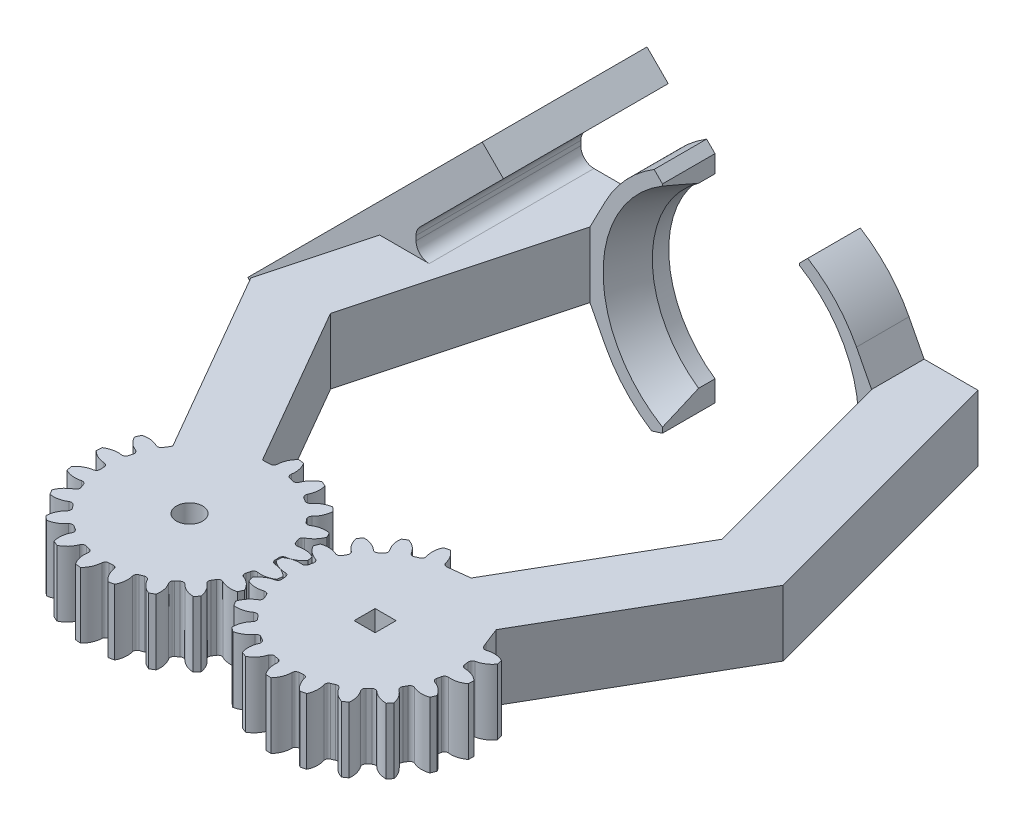
SolidWorks part; units mm, degrees
ref_plane "Front Plane" through (0, 0, 0) normal (0, 0, 1) x (1, 0, 0)
ref_plane "Top Plane" through (0, 0, 0) normal (0, 1, 0) x (1, 0, 0)
ref_plane "Right Plane" through (0, 0, 0) normal (1, 0, 0) x (0, 0, -1)
sketch "Sketch1" plane through (0, 0, 0) normal (0, 1, 0) x (1, 0, 0)
  line L0 (-1.5124, 12.6196) -> (-15.6699, 37.141)
  line L1 (-10.1727, 7.6196) -> (-25.6699, 34.4615)
  line L2 (29.9646, 12.9427) -> (43.9355, 37.141)
  line L3 (38.6794, 8.0371) -> (53.9355, 34.4615)
  line L4 (-13.3963, -7.7344) -> (-13.3913, -7.7315)
  line L5 (-13.1804, -8.0969) -> (-13.6023, -7.3661)
  line L6 (-10.3506, -11.4955) -> (-10.3468, -11.4912)
  line L7 (-10.0332, -11.7735) -> (-10.6603, -11.209)
  line L8 (-6.2917, -14.1314) -> (-6.2894, -14.1261)
  line L9 (-5.904, -14.2977) -> (-6.6748, -13.9546)
  line L10 (-1.6169, -15.384) -> (-1.6163, -15.3783)
  line L11 (-1.1968, -15.4224) -> (-2.0359, -15.3342)
  line L12 (3.2161, -15.1307) -> (3.2149, -15.1251)
  line L13 (3.6276, -15.0374) -> (2.8023, -15.2128)
  line L14 (7.7344, -13.3963) -> (7.7315, -13.3913)
  line L15 (8.0969, -13.1804) -> (7.3661, -13.6023)
  line L16 (11.4955, -10.3506) -> (11.4912, -10.3468)
  line L17 (11.7735, -10.0332) -> (11.209, -10.6603)
  line L18 (14.1314, -6.2917) -> (14.1261, -6.2894)
  line L19 (14.2977, -5.904) -> (13.9546, -6.6748)
  line L20 (15.384, -1.6169) -> (15.3783, -1.6163)
  line L21 (15.4224, -1.1968) -> (15.3342, -2.0359)
  line L22 (15.1307, 3.2161) -> (15.1251, 3.2149)
  line L23 (15.0374, 3.6276) -> (15.2128, 2.8023)
  line L24 (13.3963, 7.7344) -> (13.3913, 7.7315)
  line L25 (13.1804, 8.0969) -> (13.6023, 7.3661)
  line L26 (10.3506, 11.4955) -> (10.3468, 11.4912)
  line L27 (10.0332, 11.7735) -> (10.6603, 11.209)
  line L28 (6.2917, 14.1314) -> (6.2894, 14.1261)
  line L29 (5.904, 14.2977) -> (6.6748, 13.9546)
  line L30 (1.6169, 15.384) -> (1.6163, 15.3783)
  line L31 (1.1968, 15.4224) -> (2.0359, 15.3342)
  line L32 (-14.1314, 6.2917) -> (-14.1261, 6.2894)
  line L33 (-14.2977, 5.904) -> (-13.9546, 6.6748)
  line L34 (-15.384, 1.6169) -> (-15.3783, 1.6163)
  line L35 (-15.4224, 1.1968) -> (-15.3342, 2.0359)
  line L36 (-15.1307, -3.2161) -> (-15.1251, -3.2149)
  line L37 (-15.0374, -3.6276) -> (-15.2128, -2.8023)
  line L38 (-9.6435, -8.1965) -> (-10.0224, -7.7286)
  line L39 (-6.6387, -10.7754) -> (-7.1436, -10.4475)
  line L40 (-2.984, -12.2995) -> (-3.5655, -12.1436)
  line L41 (0.9628, -12.6196) -> (0.3616, -12.6511)
  line L42 (4.8154, -11.7044) -> (4.2533, -11.9202)
  line L43 (8.1965, -9.6435) -> (7.7286, -10.0224)
  line L44 (10.7754, -6.6387) -> (10.4475, -7.1436)
  line L45 (12.2995, -2.984) -> (12.1436, -3.5655)
  line L46 (12.6196, 0.9628) -> (12.6511, 0.3616)
  line L47 (11.7044, 4.8154) -> (11.9202, 4.2533)
  line L48 (9.6435, 8.1965) -> (10.0224, 7.7286)
  line L49 (6.6387, 10.7754) -> (7.1436, 10.4475)
  line L50 (2.984, 12.2995) -> (3.5655, 12.1436)
  line L51 (-0.9628, 12.6196) -> (-0.3616, 12.6511)
  line L52 (-10.7754, 6.6387) -> (-10.4475, 7.1436)
  line L53 (-12.2995, 2.984) -> (-12.1436, 3.5655)
  line L54 (-12.6196, -0.9628) -> (-12.6511, -0.3616)
  line L55 (-11.7044, -4.8154) -> (-11.9202, -4.2533)
  line L56 (43.7132, -0.8096) -> (43.7074, -0.8093)
  line L57 (43.6854, -1.2306) -> (43.7295, -0.388)
  line L58 (42.707, -5.5435) -> (42.7016, -5.5414)
  line L59 (42.5504, -5.9353) -> (42.8528, -5.1476)
  line L60 (40.2871, -9.7348) -> (40.2826, -9.7312)
  line L61 (40.0172, -10.059) -> (40.5481, -9.4033)
  line L62 (36.6905, -12.9732) -> (36.6874, -12.9684)
  line L63 (36.3336, -13.1981) -> (37.0412, -12.7386)
  line L64 (32.2693, -14.9417) -> (32.2678, -14.9361)
  line L65 (31.8603, -15.0453) -> (32.6753, -14.8269)
  line L66 (27.4561, -15.4476) -> (27.4564, -15.4418)
  line L67 (27.0351, -15.4197) -> (27.8777, -15.4639)
  line L68 (22.7221, -14.4413) -> (22.7242, -14.436)
  line L69 (22.3303, -14.2848) -> (23.1181, -14.5871)
  line L70 (18.5308, -12.0215) -> (18.5345, -12.017)
  line L71 (18.2066, -11.7515) -> (18.8623, -12.2825)
  line L72 (15.2925, -8.4249) -> (15.2973, -8.4218)
  line L73 (15.0675, -8.0679) -> (15.5271, -8.7756)
  line L74 (13.324, -4.0036) -> (13.3295, -4.0021)
  line L75 (13.2203, -3.5946) -> (13.4387, -4.4096)
  line L76 (12.8181, 0.8096) -> (12.8238, 0.8093)
  line L77 (12.8459, 1.2306) -> (12.8018, 0.388)
  line L78 (13.8243, 5.5435) -> (13.8297, 5.5414)
  line L79 (13.9809, 5.9353) -> (13.6785, 5.1476)
  line L80 (16.2442, 9.7348) -> (16.2486, 9.7312)
  line L81 (16.5141, 10.059) -> (15.9831, 9.4033)
  line L82 (19.8408, 12.9732) -> (19.8439, 12.9684)
  line L83 (20.1977, 13.1981) -> (19.4901, 12.7386)
  line L84 (24.262, 14.9417) -> (24.2635, 14.9361)
  line L85 (24.671, 15.0453) -> (23.856, 14.8269)
  line L86 (43.2073, 4.0036) -> (43.2018, 4.0021)
  line L87 (43.3109, 3.5946) -> (43.0926, 4.4096)
  line L88 (40.5792, -2.9251) -> (40.7044, -2.3362)
  line L89 (39.0727, -6.5871) -> (39.3737, -6.0656)
  line L90 (36.5082, -9.6042) -> (36.9557, -9.2013)
  line L91 (33.1369, -11.6812) -> (33.687, -11.4363)
  line L92 (29.2888, -12.6148) -> (29.8876, -12.5519)
  line L93 (25.3405, -12.3136) -> (25.9295, -12.4388)
  line L94 (21.6786, -10.807) -> (22.2, -11.1081)
  line L95 (18.6614, -8.2426) -> (19.0643, -8.69)
  line L96 (16.5844, -4.8713) -> (16.8293, -5.4213)
  line L97 (15.6508, -1.0232) -> (15.7138, -1.622)
  line L98 (15.9521, 2.9251) -> (15.8269, 2.3362)
  line L99 (17.4586, 6.5871) -> (17.1576, 6.0656)
  line L100 (20.0231, 9.6042) -> (19.5756, 9.2013)
  line L101 (23.3944, 11.6812) -> (22.8443, 11.4363)
  line L102 (27.2425, 12.6148) -> (26.6437, 12.5519)
  line L103 (39.9469, 4.8713) -> (39.702, 5.4213)
  line L104 (40.8805, 1.0232) -> (40.8175, 1.622)
  line L105 (27.2425, 12.6148) -> (29.9646, 12.9427)
  line L106 (39.702, 5.4213) -> (38.6794, 8.0371)
  line L107 (-10.4475, 7.1436) -> (-10.1727, 7.6196)
  line L108 (-0.9628, 12.6196) -> (-1.5124, 12.6196)
  line L109 (-15.6699, 37.141) -> (-5.3171, 75.778)
  line L110 (-5.3171, 75.778) -> (-14.9764, 78.3662)
  line L111 (-14.9764, 78.3662) -> (-26.4012, 35.7282)
  line L112 (-25.6699, 34.4615) -> (-26.4012, 35.7282)
  line L113 (43.9355, 37.141) -> (33.5828, 75.778)
  line L114 (33.5828, 75.778) -> (43.242, 78.3662)
  line L115 (43.242, 78.3662) -> (54.6668, 35.7282)
  line L116 (53.9355, 34.4615) -> (54.6668, 35.7282)
  circle A0 centre (0, 0) radius 2
  circle A1 centre (28.2656, 0) radius 2
  arc A2 (-13.1804, -8.0969) -> (-10.7748, -7.6007) centre (-12.61, -4.7824) ccw
  arc A3 (-10.0224, -7.7286) -> (-10.7748, -7.6007) centre (-10.4679, -8.0721) ccw
  arc A4 (-11.9698, -5.5309) -> (-13.6023, -7.3661) centre (-10.4467, -8.5294) ccw
  arc A5 (-11.9698, -5.5309) -> (-11.7044, -4.8154) centre (-12.2246, -5.0294) ccw
  arc A6 (-10.0332, -11.7735) -> (-7.8987, -10.5583) centre (-10.515, -8.4451) ccw
  arc A7 (-7.1436, -10.4475) -> (-7.8987, -10.5583) centre (-7.4611, -10.9118) ccw
  arc A8 (-9.6749, -8.9591) -> (-10.6603, -11.209) centre (-7.2997, -11.3401) ccw
  arc A9 (-9.6749, -8.9591) -> (-9.6435, -8.1965) centre (-10.0721, -8.5608) ccw
  arc A10 (-5.904, -14.2977) -> (-4.2494, -12.4824) centre (-7.3907, -11.281) ccw
  arc A11 (-3.5655, -12.1436) -> (-4.2494, -12.4824) centre (-3.724, -12.6833) ccw
  arc A12 (-6.4328, -11.5103) -> (-6.6748, -13.9546) centre (-3.4381, -13.0408) ccw
  arc A13 (-6.4328, -11.5103) -> (-6.6387, -10.7754) centre (-6.9337, -11.2543) ccw
  arc A14 (-1.1968, -15.4224) -> (-0.1841, -13.1846) centre (-3.5429, -13.0127) ccw
  arc A15 (0.3616, -12.6511) -> (-0.1841, -13.1846) centre (0.3776, -13.2134) ccw
  arc A16 (-2.5611, -12.9348) -> (-2.0359, -15.3342) centre (0.76, -13.465) ccw
  arc A17 (-2.5611, -12.9348) -> (-2.984, -12.2995) centre (-3.1166, -12.8461) ccw
  arc A18 (3.6276, -15.0374) -> (3.8991, -12.5962) centre (0.6517, -13.4707) ccw
  arc A19 (4.2533, -11.9202) -> (3.8991, -12.5962) centre (4.4423, -12.45) ccw
  arc A20 (1.5613, -13.0931) -> (2.8023, -15.2128) centre (4.8837, -12.5711) ccw
  arc A21 (1.5613, -13.0931) -> (0.9628, -12.6196) centre (1.0056, -13.1804) ccw
  arc A22 (8.0969, -13.1804) -> (7.6007, -10.7748) centre (4.7824, -12.61) ccw
  arc A23 (7.7286, -10.0224) -> (7.6007, -10.7748) centre (8.0721, -10.4679) ccw
  arc A24 (5.5309, -11.9698) -> (7.3661, -13.6023) centre (8.5294, -10.4467) ccw
  arc A25 (5.5309, -11.9698) -> (4.8154, -11.7044) centre (5.0294, -12.2246) ccw
  arc A26 (11.7735, -10.0332) -> (10.5583, -7.8987) centre (8.4451, -10.515) ccw
  arc A27 (10.4475, -7.1436) -> (10.5583, -7.8987) centre (10.9118, -7.4611) ccw
  arc A28 (8.9591, -9.6749) -> (11.209, -10.6603) centre (11.3401, -7.2997) ccw
  arc A29 (8.9591, -9.6749) -> (8.1965, -9.6435) centre (8.5608, -10.0721) ccw
  arc A30 (14.2977, -5.904) -> (12.4824, -4.2494) centre (11.281, -7.3907) ccw
  arc A31 (12.1436, -3.5655) -> (12.4824, -4.2494) centre (12.6833, -3.724) ccw
  arc A32 (11.5103, -6.4328) -> (13.9546, -6.6748) centre (13.0408, -3.4381) ccw
  arc A33 (11.5103, -6.4328) -> (10.7754, -6.6387) centre (11.2543, -6.9337) ccw
  arc A34 (15.4224, -1.1968) -> (13.1846, -0.1841) centre (13.0127, -3.5429) ccw
  arc A35 (12.6511, 0.3616) -> (13.1846, -0.1841) centre (13.2134, 0.3776) ccw
  arc A36 (12.9348, -2.5611) -> (15.3342, -2.0359) centre (13.465, 0.76) ccw
  arc A37 (12.9348, -2.5611) -> (12.2995, -2.984) centre (12.8461, -3.1166) ccw
  arc A38 (15.0374, 3.6276) -> (12.5962, 3.8991) centre (13.4707, 0.6517) ccw
  arc A39 (11.9202, 4.2533) -> (12.5962, 3.8991) centre (12.45, 4.4423) ccw
  arc A40 (13.0931, 1.5613) -> (15.2128, 2.8023) centre (12.5711, 4.8837) ccw
  arc A41 (13.0931, 1.5613) -> (12.6196, 0.9628) centre (13.1804, 1.0056) ccw
  arc A42 (13.1804, 8.0969) -> (10.7748, 7.6007) centre (12.61, 4.7824) ccw
  arc A43 (10.0224, 7.7286) -> (10.7748, 7.6007) centre (10.4679, 8.0721) ccw
  arc A44 (11.9698, 5.5309) -> (13.6023, 7.3661) centre (10.4467, 8.5294) ccw
  arc A45 (11.9698, 5.5309) -> (11.7044, 4.8154) centre (12.2246, 5.0294) ccw
  arc A46 (10.0332, 11.7735) -> (7.8987, 10.5583) centre (10.515, 8.4451) ccw
  arc A47 (7.1436, 10.4475) -> (7.8987, 10.5583) centre (7.4611, 10.9118) ccw
  arc A48 (9.6749, 8.9591) -> (10.6603, 11.209) centre (7.2997, 11.3401) ccw
  arc A49 (9.6749, 8.9591) -> (9.6435, 8.1965) centre (10.0721, 8.5608) ccw
  arc A50 (5.904, 14.2977) -> (4.2494, 12.4824) centre (7.3907, 11.281) ccw
  arc A51 (3.5655, 12.1436) -> (4.2494, 12.4824) centre (3.724, 12.6833) ccw
  arc A52 (6.4328, 11.5103) -> (6.6748, 13.9546) centre (3.4381, 13.0408) ccw
  arc A53 (6.4328, 11.5103) -> (6.6387, 10.7754) centre (6.9337, 11.2543) ccw
  arc A54 (1.1968, 15.4224) -> (0.1841, 13.1846) centre (3.5429, 13.0127) ccw
  arc A55 (-0.3616, 12.6511) -> (0.1841, 13.1846) centre (-0.3776, 13.2134) ccw
  arc A56 (2.5611, 12.9348) -> (2.0359, 15.3342) centre (-0.76, 13.465) ccw
  arc A57 (2.5611, 12.9348) -> (2.984, 12.2995) centre (3.1166, 12.8461) ccw
  arc A58 (-14.2977, 5.904) -> (-12.4824, 4.2494) centre (-11.281, 7.3907) ccw
  arc A59 (-12.1436, 3.5655) -> (-12.4824, 4.2494) centre (-12.6833, 3.724) ccw
  arc A60 (-11.5103, 6.4328) -> (-13.9546, 6.6748) centre (-13.0408, 3.4381) ccw
  arc A61 (-11.5103, 6.4328) -> (-10.7754, 6.6387) centre (-11.2543, 6.9337) ccw
  arc A62 (-15.4224, 1.1968) -> (-13.1846, 0.1841) centre (-13.0127, 3.5429) ccw
  arc A63 (-12.6511, -0.3616) -> (-13.1846, 0.1841) centre (-13.2134, -0.3776) ccw
  arc A64 (-12.9348, 2.5611) -> (-15.3342, 2.0359) centre (-13.465, -0.76) ccw
  arc A65 (-12.9348, 2.5611) -> (-12.2995, 2.984) centre (-12.8461, 3.1166) ccw
  arc A66 (-15.0374, -3.6276) -> (-12.5962, -3.8991) centre (-13.4707, -0.6517) ccw
  arc A67 (-11.9202, -4.2533) -> (-12.5962, -3.8991) centre (-12.45, -4.4423) ccw
  arc A68 (-13.0931, -1.5613) -> (-15.2128, -2.8023) centre (-12.5711, -4.8837) ccw
  arc A69 (-13.0931, -1.5613) -> (-12.6196, -0.9628) centre (-13.1804, -1.0056) ccw
  arc A70 (41.3167, -1.8806) -> (43.6854, -1.2306) centre (41.6724, 1.4636) ccw
  arc A71 (41.3167, -1.8806) -> (40.7044, -2.3362) centre (41.2572, -2.44) ccw
  arc A72 (43.7295, -0.388) -> (41.4418, 0.5061) centre (41.446, -2.857) ccw
  arc A73 (40.8805, 1.0232) -> (41.4418, 0.5061) centre (41.4411, 1.0686) ccw
  arc A74 (40.0968, -5.8216) -> (42.5504, -5.9353) centre (41.4685, -2.7509) ccw
  arc A75 (40.0968, -5.8216) -> (39.3737, -6.0656) centre (39.8674, -6.3352) ccw
  arc A76 (42.8528, -5.1476) -> (40.9533, -3.5903) centre (39.918, -6.7901) ccw
  arc A77 (40.5792, -2.9251) -> (40.9533, -3.5903) centre (41.1265, -3.0551) ccw
  arc A78 (37.7188, -9.1927) -> (40.0172, -10.059) centre (39.9722, -6.6962) ccw
  arc A79 (37.7188, -9.1927) -> (36.9557, -9.2013) centre (37.3419, -9.6103) ccw
  arc A80 (40.5481, -9.4033) -> (39.2229, -7.3353) centre (37.2494, -10.0586) ccw
  arc A81 (39.0727, -6.5871) -> (39.2229, -7.3353) centre (39.553, -6.8798) ccw
  arc A82 (34.4154, -11.664) -> (36.3336, -13.1981) centre (37.33, -9.986) ccw
  arc A83 (34.4154, -11.664) -> (33.687, -11.4363) centre (33.9279, -11.9446) ccw
  arc A84 (37.0412, -12.7386) -> (36.4199, -10.3623) centre (33.7015, -12.3424) ccw
  arc A85 (36.5082, -9.6042) -> (36.4199, -10.3623) centre (36.8745, -10.0311) ccw
  arc A86 (30.51, -12.9935) -> (31.8603, -15.0453) centre (33.8006, -12.2983) ccw
  arc A87 (30.51, -12.9935) -> (29.8876, -12.5519) centre (29.9597, -13.1097) ccw
  arc A88 (32.6753, -14.8269) -> (32.8187, -12.3749) centre (29.6214, -13.4181) ccw
  arc A89 (33.1369, -11.6812) -> (32.8187, -12.3749) centre (33.3534, -12.2004) ccw
  arc A90 (26.385, -13.0511) -> (27.0351, -15.4197) centre (29.7293, -13.4068) ccw
  arc A91 (26.385, -13.0511) -> (25.9295, -12.4388) centre (25.8256, -12.9916) ccw
  arc A92 (27.8777, -15.4639) -> (28.7718, -13.1762) centre (25.4086, -13.1803) ccw
  arc A93 (29.2888, -12.6148) -> (28.7718, -13.1762) centre (29.3343, -13.1755) ccw
  arc A94 (22.444, -11.8312) -> (22.3303, -14.2848) centre (25.5147, -13.2029) ccw
  arc A95 (22.444, -11.8312) -> (22.2, -11.1081) centre (21.9304, -11.6017) ccw
  arc A96 (23.1181, -14.5871) -> (24.6753, -12.6877) centre (21.4755, -11.6524) ccw
  arc A97 (25.3405, -12.3136) -> (24.6753, -12.6877) centre (25.2105, -12.8609) ccw
  arc A98 (19.0729, -9.4531) -> (18.2066, -11.7515) centre (21.5695, -11.7066) ccw
  arc A99 (19.0729, -9.4531) -> (19.0643, -8.69) centre (18.6554, -9.0762) ccw
  arc A100 (18.8623, -12.2825) -> (20.9304, -10.9573) centre (18.2071, -8.9838) ccw
  arc A101 (21.6786, -10.807) -> (20.9304, -10.9573) centre (21.3858, -11.2873) ccw
  arc A102 (16.6017, -6.1498) -> (15.0675, -8.0679) centre (18.2796, -9.0644) ccw
  arc A103 (16.6017, -6.1498) -> (16.8293, -5.4213) centre (16.321, -5.6623) ccw
  arc A104 (15.5271, -8.7756) -> (17.9034, -8.1542) centre (15.9232, -5.4358) ccw
  arc A105 (18.6614, -8.2426) -> (17.9034, -8.1542) centre (18.2346, -8.6089) ccw
  arc A106 (15.2722, -2.2444) -> (13.2203, -3.5946) centre (15.9673, -5.5349) ccw
  arc A107 (15.2722, -2.2444) -> (15.7138, -1.622) centre (15.1559, -1.6941) ccw
  arc A108 (13.4387, -4.4096) -> (15.8908, -4.553) centre (14.8475, -1.3558) ccw
  arc A109 (16.5844, -4.8713) -> (15.8908, -4.553) centre (16.0652, -5.0878) ccw
  arc A110 (15.2146, 1.8806) -> (12.8459, 1.2306) centre (14.8589, -1.4636) ccw
  arc A111 (15.2146, 1.8806) -> (15.8269, 2.3362) centre (15.274, 2.44) ccw
  arc A112 (12.8018, 0.388) -> (15.0895, -0.5061) centre (15.0853, 2.857) ccw
  arc A113 (15.6508, -1.0232) -> (15.0895, -0.5061) centre (15.0902, -1.0686) ccw
  arc A114 (16.4345, 5.8216) -> (13.9809, 5.9353) centre (15.0628, 2.7509) ccw
  arc A115 (16.4345, 5.8216) -> (17.1576, 6.0656) centre (16.6639, 6.3352) ccw
  arc A116 (13.6785, 5.1476) -> (15.578, 3.5903) centre (16.6133, 6.7901) ccw
  arc A117 (15.9521, 2.9251) -> (15.578, 3.5903) centre (15.4048, 3.0551) ccw
  arc A118 (18.8125, 9.1927) -> (16.5141, 10.059) centre (16.559, 6.6962) ccw
  arc A119 (18.8125, 9.1927) -> (19.5756, 9.2013) centre (19.1894, 9.6103) ccw
  arc A120 (15.9831, 9.4033) -> (17.3084, 7.3353) centre (19.2818, 10.0586) ccw
  arc A121 (17.4586, 6.5871) -> (17.3084, 7.3353) centre (16.9783, 6.8798) ccw
  arc A122 (22.1159, 11.664) -> (20.1977, 13.1981) centre (19.2012, 9.986) ccw
  arc A123 (22.1159, 11.664) -> (22.8443, 11.4363) centre (22.6034, 11.9446) ccw
  arc A124 (19.4901, 12.7386) -> (20.1114, 10.3623) centre (22.8298, 12.3424) ccw
  arc A125 (20.0231, 9.6042) -> (20.1114, 10.3623) centre (19.6567, 10.0311) ccw
  arc A126 (26.0212, 12.9935) -> (24.671, 15.0453) centre (22.7307, 12.2983) ccw
  arc A127 (26.0212, 12.9935) -> (26.6437, 12.5519) centre (26.5716, 13.1097) ccw
  arc A128 (23.856, 14.8269) -> (23.7126, 12.3749) centre (26.9099, 13.4181) ccw
  arc A129 (23.3944, 11.6812) -> (23.7126, 12.3749) centre (23.1779, 12.2004) ccw
  arc A130 (41.2591, 2.2444) -> (43.3109, 3.5946) centre (40.5639, 5.5349) ccw
  arc A131 (41.2591, 2.2444) -> (40.8175, 1.622) centre (41.3754, 1.6941) ccw
  arc A132 (43.0926, 4.4096) -> (40.6405, 4.553) centre (41.6837, 1.3558) ccw
  arc A133 (39.9469, 4.8713) -> (40.6405, 4.553) centre (40.466, 5.0878) ccw
extrude "Boss-Extrude1" add sketch "Sketch1" along normal blind 10 contours A133 L103 L106 L3 L116 L115 L114 L113 L2 L105 L102 A127 A126 L85 A128 A129 L101 A123 A122 L83 A124 A125 L100 A119 A118 L81 A120 A121 L99 A115 A114 L79 A116 A117 L98 A111 A110 L77 A112 A113 L97 A107 A106 L75 A108 | A69 A68 L37 A66 A67 L55 A5 A4 L5 A2 A3 L38 A9 A8 L7 A6 A7 L39 A13 A12 L9 A10 A11 L40 A17 A16 L11 A14 A15 L41 A21 A20 L13 A18 A19 L42 A25 A24 L15 A22 A23 L43 A29 A28 region at (-8.072, 0, -23.4532) region at (36.3461, 0, -23.5032)
sketch "Sketch2" plane through (0, 0, 0) normal (0, -1, 0) x (1, 0, 0)
  line L1 (-7.3171, -75.778) -> (-7.3171, -68.3139)
  line L2 (-15.6699, -37.141) -> (-5.3171, -75.778) construction
  line L3 (-7.3171, -75.778) -> (-7.3171, -76.3139)
  line L4 (-5.3171, -75.778) -> (-14.9764, -78.3662) construction
  line L5 (-7.3171, -68.3139) -> (-5.3171, -75.778)
  line L6 (-7.3171, -76.3139) -> (-5.3171, -75.778)
  line L8 (35.5828, -68.3139) -> (35.5828, -76.3139)
  line L9 (43.9355, -37.141) -> (33.5828, -75.778) construction
  line L11 (33.5828, -75.778) -> (43.242, -78.3662) construction
  line L15 (35.5828, -76.3139) -> (33.5828, -75.778)
  line L16 (33.5828, -75.778) -> (35.5828, -68.3139)
  dimension "D1" = 8
  dimension "D3" = 8
extrude "Cut-Extrude1" cut sketch "Sketch2" against normal through all
sketch "Sketch4" plane through (-7.3171, 0, 0) normal (1, 0, 0) x (0, 0, -1)
  line L0 (68.3139, 5) -> (68.3139, 25)
  line L1 (68.3139, 10) -> (68.3139, 0) construction
  line L2 (68.3139, 5) -> (68.3139, -15)
  line L4 (76.3139, 0) -> (76.3139, -15)
  line L5 (76.3139, -15) -> (68.3139, -15)
  line L7 (76.3139, 10) -> (76.3139, 25)
  line L8 (76.3139, 25) -> (68.3139, 25)
  line L9 (76.3139, 0) -> (76.3139, 10)
  dimension "D1" = 20
  dimension "D2" = 20
extrude "Boss-Extrude2" add sketch "Sketch4" along normal blind 20.5
sketch "Sketch5" plane through (35.5828, 0, 0) normal (-1, 0, 0) x (0, 0, 1)
  line L1 (-68.3139, 5) -> (-68.3139, 35)
  line L2 (-68.3139, 10) -> (-68.3139, 0) construction
  line L3 (-76.3139, 5) -> (-76.3139, -25)
  line L4 (-76.3139, 10) -> (-76.3139, 0) construction
  line L6 (-68.3139, 5) -> (-68.3139, -25)
  line L8 (-76.3139, 5) -> (-76.3139, 35)
  line L10 (-68.3139, 35) -> (-76.3139, 35)
  line L12 (-76.3139, -25) -> (-68.3139, -25)
  dimension "D1" = 30
  dimension "D2" = 30
  dimension "D3" = 30
  dimension "D4" = 30
sketch "Sketch6" plane through (0, 0, -68.3139) normal (0, 0, 1) x (1, 0, 0)
  line L0 (13.1829, 25) -> (13.1829, -15) construction
  line L3 (-7.3171, 0) -> (-5.015, -4.4385)
  line L4 (-7.3171, 10) -> (-5.015, 14.4385)
  line L7 (-7.3171, 0) -> (-7.3171, 10)
  line L9 (8.7279, 25.0101) -> (8.7279, 20.8872)
  line L10 (8.7279, -10.8872) -> (8.7279, -15.0101)
  line L12 (-7.3171, 25) -> (13.1829, 25)
  line L13 (-7.3171, 25) -> (-7.3171, -15)
  line L14 (-7.3171, -15) -> (13.1829, -15)
  line L15 (13.1829, 25) -> (13.1829, -15)
  arc A0 (8.7279, 20.8872) -> (8.7279, -10.8872) centre (13.1829, 5) ccw
  arc A2 (-5.015, -4.4385) -> (8.7279, -15.0101) centre (13.1829, 5) ccw
  arc A3 (8.7279, 25.0101) -> (-5.015, 14.4385) centre (13.1829, 5) ccw
  line M5 (-7.3171, 25) -> (-7.3171, 10)
  line M7 (-7.3171, 0) -> (-7.3171, -15)
  line M8 (-7.3171, -15) -> (13.1829, -15)
  line M9 (13.1829, -15) -> (13.1829, 25)
  line M10 (13.1829, 25) -> (-7.3171, 25)
  dimension "D1" = 33
extrude "Cut-Extrude9" cut sketch "Sketch6" against normal blind 20.5 contours A2 L3 M7 M8 | L9 A0 L10 M8 M9 M10 | A3 L12 L4 M5 region at (-3.0986, -10.7161, -68.3139) region at (-3.0986, 20.7161, -68.3139) region at (6.5177, 5, -68.3139)
extrude "Boss-Extrude3" add sketch "Sketch5" along normal blind 20.5
sketch "Sketch9" plane through (0, 0, -68.3139) normal (0, 0, 1) x (1, 0, 0)
  line L13 (15.0828, -25) -> (15.0828, 35) construction
  line L14 (35.5828, 10) -> (35.5828, 0)
  line L24 (35.5828, 10) -> (35.5828, 0)
  line L25 (35.5828, 0) -> (33.2807, -4.4385)
  line L26 (35.5828, 10) -> (33.2807, 14.4385)
  line L27 (19.5828, 20.8745) -> (19.5828, 25)
  line L28 (19.5828, -10.8745) -> (19.5828, -15)
  arc A7 (19.5828, -10.8745) -> (19.5828, 20.8745) centre (15.0828, 5) ccw
  arc A8 (19.5828, -15) -> (33.2807, -4.4385) centre (15.0828, 5) ccw
  arc A9 (19.5828, -15) -> (33.2807, -4.4385) centre (15.0828, 5) ccw
  arc A10 (33.2807, 14.4385) -> (19.5828, 25) centre (15.0828, 5) ccw
  line M5 (35.5828, -25) -> (35.5828, 0)
  line M7 (35.5828, 10) -> (35.5828, 35)
  line M8 (35.5828, 35) -> (15.0828, 35)
  line M9 (15.0828, 35) -> (15.0828, -25)
  line M10 (15.0828, -25) -> (35.5828, -25)
  dimension "D1" = 33
extrude "Cut-Extrude32" cut sketch "Sketch9" against normal blind 20.5 contours A10 L26 L25 A8 L28 A7 L27 M7 M8 M9 M10 M5 region at (24.6582, 5, -68.3139)
sketch "Sketch10" plane through (0, 0, 0) normal (0, -1, 0) x (1, 0, 0)
  line L0 (-7.3171, -76.3139) -> (-15.5263, -76.3139)
  line L1 (-14.9764, -78.3662) -> (-26.4012, -35.7282) construction
  line L2 (-15.5263, -76.3139) -> (-14.9764, -78.3662)
  line L3 (-14.9764, -78.3662) -> (-7.3171, -76.3139)
  line L4 (35.5828, -76.3139) -> (43.7919, -76.3139)
  line L5 (43.242, -78.3662) -> (54.6668, -35.7282) construction
  line L6 (43.7919, -76.3139) -> (43.242, -78.3662)
  line L7 (43.242, -78.3662) -> (35.5828, -76.3139)
extrude "Cut-Extrude33" cut sketch "Sketch10" against normal blind 20.5
sketch "Sketch16" plane through (0, 10, 0) normal (0, 1, 0) x (1, 0, 0)
  line L1 (26.6656, -1.6) -> (29.8656, -1.6)
  line L2 (26.6656, -1.6) -> (26.6656, 1.6)
  line L3 (26.6656, 1.6) -> (29.8656, 1.6)
  line L4 (29.8656, -1.6) -> (29.8656, 1.6)
  line L5 (26.6656, -1.6) -> (29.8656, 1.6) construction
  line L6 (26.6656, 1.6) -> (29.8656, -1.6) construction
  circle A0 centre (28.2656, 0) radius 2
  point P0 (28.2656, 0)
  dimension "D1" = 3.2
  dimension "D2" = 3.2
extrude "Boss-Extrude7" add sketch "Sketch16" against normal blind 5 contours L3 A0 | L4 A0 | L1 A0 | L2 A0 region at (28.2656, 10, 1.7615) region at (26.5042, 10, 0) region at (30.0271, 10, 0) region at (28.2656, 10, -1.7615)
sketch "Sketch17" plane through (0, 10, 0) normal (0, 1, 0) x (1, 0, 0)
  line L1 (26.6656, -1.6) -> (29.8656, -1.6)
  line L2 (26.6656, -1.6) -> (26.6656, 1.6)
  line L3 (26.6656, 1.6) -> (29.8656, 1.6)
  line L4 (29.8656, -1.6) -> (29.8656, 1.6)
  line L5 (26.6656, -1.6) -> (29.8656, 1.6) construction
  line L6 (26.6656, 1.6) -> (29.8656, -1.6) construction
  circle A0 centre (28.2656, 0) radius 2
  point P0 (28.2656, 0)
  dimension "D1" = 3.2
  dimension "D2" = 3.2
extrude "Cut-Extrude35" cut sketch "Sketch17" against normal blind 5 contours A0 L3 L2 | A0 L4 L3 | A0 L1 L4 | A0 L2 L1 region at (26.7926, 10, 1.4731) region at (29.7387, 10, 1.4731) region at (26.7926, 10, -1.4731) region at (29.7387, 10, -1.4731)
sketch "Sketch18" plane through (0, 0, -68.3139) normal (0, 0, 1) x (1, 0, 0)
  line L0 (19.5828, 25) -> (19.5828, 20.8745)
  line L2 (3.7279, -8.5223) -> (3.7279, -13.1894)
  line L6 (24.5828, -13.1659) -> (24.5828, -8.4907)
  line L8 (19.5828, -10.8745) -> (19.5828, -15)
  line L9 (24.5828, 25) -> (24.5828, 14.9269)
  line L11 (3.7279, 23.1823) -> (3.7279, 14.9269)
  line L12 (3.7279, 14.9269) -> (10.8868, 14.9269)
  line L13 (10.8868, 23.1823) -> (10.8868, 14.9269)
  line L15 (3.7279, 23.1823) -> (3.7279, 32.214)
  line L16 (3.7279, 32.214) -> (10.8868, 32.214)
  line L17 (10.8868, 23.1823) -> (10.8868, 32.214)
  line L18 (3.7279, -8.5223) -> (11.4152, -8.5223)
  line L19 (3.7279, -8.5223) -> (3.7279, -24.2522)
  line L20 (3.7279, -24.2522) -> (11.4152, -24.2522)
  line L21 (11.4152, -8.5223) -> (11.4152, -24.2522)
  line L22 (19.5828, -15) -> (24.5828, -15)
  line L23 (19.5828, -15) -> (19.5828, -3.87)
  line L24 (19.5828, -3.87) -> (24.5828, -3.87)
  line L25 (24.5828, -15) -> (24.5828, -3.87)
  line L26 (19.5828, 25) -> (24.5828, 25)
  line L27 (19.5828, 25) -> (19.5828, 14.9269)
  line L28 (19.5828, 14.9269) -> (24.5828, 14.9269)
  arc A1 (-5.015, -4.4385) -> (8.6829, -15) centre (13.1829, 5) ccw construction
  arc M10 (19.5828, -15) -> (33.2807, -4.4385) centre (15.0828, 5) ccw
  arc M14 (33.2807, 14.4385) -> (19.5828, 25) centre (15.0828, 5) ccw
  line M15 (19.5828, 25) -> (19.5828, 20.8745)
  arc M16 (19.5828, 20.8745) -> (19.5828, -10.8745) centre (15.0828, 5) cw
  line M17 (19.5828, -10.8745) -> (19.5828, -15)
extrude "Cut-Extrude36" cut sketch "Sketch18" against normal through all contours M16 M14 M15 | L6 M10 M16 M17 | L2 | L15 L16 L17 L13 L12 L11 | L23 L22 L25 L24 | L26 L9 L28 L27 region at (22.1345, 22.0091, -68.3139) region at (22.1345, -12.0091, -68.3139) region at (7.5716, -16.3873, -68.3139)
chamfer "Chamfer4" distance 2 angle 70 1 edges at (31.5828, 5, -68.3139) first distance on face at (30.55, 5, -68.3139)
chamfer "Chamfer5" distance 2 angle 70 1 edges at (-3.3171, 5, -68.3139) first distance on face at (-2.2687, 5, -68.3139)
sketch "Sketch19" plane through (0, 10, 0) normal (0, 1, 0) x (1, 0, 0)
  line L0 (-15.5263, 76.3139) -> (-22.2518, 76.3139)
  line L1 (-22.2518, 76.3139) -> (-22.2518, 51.2139)
  line L2 (-15.5263, 76.3139) -> (-26.4012, 35.7282) construction
  line L3 (-15.5263, 76.3139) -> (-22.2518, 51.2139)
  dimension "D1" = 25.1
extrude "Boss-Extrude8" add sketch "Sketch19" against normal blind 10
sketch "Sketch27" plane through (0, 0, -76.3139) normal (0, 0, -1) x (-1, 0, 0)
  line L0 (22.2518, 10) -> (20.2518, 10)
  line L1 (22.2518, 10) -> (7.3171, 10) construction
  line L2 (20.2518, 10) -> (22.2518, 8)
  line L3 (22.2518, 0) -> (22.2518, 10) construction
  dimension "D1" = 2
  dimension "D2" = 2
extrude "Cut-Extrude39" cut sketch "Sketch27" against normal blind 25.1 and the other way through all
sketch "Sketch28" plane through (-15.1259, 15.1259, 0) normal (-0.7071, 0.7071, 0) x (0, 0, 1)
  line L0 (-76.3139, -8.6633) -> (-76.3139, 16.5867)
  line L3 (-51.2139, -8.6633) -> (-51.2139, -33.9133)
  line L4 (-76.3139, -10.0775) -> (-76.3139, -7.2491) construction
  line L5 (-76.3139, 19.0334) -> (-76.3139, 6.6634) construction
  line L7 (-76.3139, 16.5867) -> (-51.2139, 16.5867)
  line L8 (-76.3139, 16.5867) -> (-76.3139, -33.9133)
  line L9 (-76.3139, -33.9133) -> (-51.2139, -33.9133)
  line L10 (-51.2139, 16.5867) -> (-51.2139, -33.9133)
  line M4 (-76.3139, -7.2491) -> (-76.3139, -10.0775)
  line M5 (-76.3139, -10.0775) -> (-51.2139, -10.0775)
  line M6 (-51.2139, -10.0775) -> (-51.2139, -7.2491)
  line M7 (-51.2139, -7.2491) -> (-76.3139, -7.2491)
  dimension "D1" = 25.25
  dimension "D2" = 25.25
extrude "Boss-Extrude11" add sketch "Sketch28" along normal blind 4.57 contours L10 L7 L0 M7 | L8 L9 L3 M5 | M7 M4 M5 M6 region at (-21.2518, 9, -63.7639) region at (-11.8246, 18.4272, -63.7639) region at (-30.679, -0.4272, -63.7639)
sketch "Sketch29" plane through (-18.3574, 18.3574, 0) normal (-0.7071, 0.7071, 0) x (0, 0, 1)
  line L0 (-76.3139, -33.9133) -> (-76.3139, 16.5867) construction
  line L1 (-51.2139, 16.5867) -> (-51.2139, -33.9133) construction
  line L2 (-76.3139, -33.9133) -> (-51.2139, -33.9133) construction
  line L3 (-76.3139, 16.5867) -> (-51.2139, 16.5867) construction
  circle A0 centre (-70.1139, 10.3867) radius 2.1
  circle A1 centre (-57.4139, 10.3867) radius 2.1
  circle A2 centre (-70.1139, -27.7133) radius 2.1
  circle A3 centre (-57.4139, -27.7133) radius 2.1
  dimension "D1" = 4.2
  dimension "D2" = 4.2
  dimension "D3" = 4.2
  dimension "D4" = 4.2
  dimension "D5" = 6.2
  dimension "D6" = 6.2
  dimension "D7" = 6.2
  dimension "D8" = 6.2
extrude "Cut-Extrude40" cut sketch "Sketch29" against normal blind 4.57
chamfer "Chamfer9" distance 5 angle 45 2 edges at (-20.2518, 10, -63.7639) (-22.2518, 8, -63.7639) first distance on face at (-9.2663, 20.9855, -57.4139) first distance on face at (-22.2518, 4, -63.7639)
chamfer "Chamfer10" distance 5 angle 45 1 edges at (-24.7518, 5.5, -63.7639)
fillet "Fillet3" radius 2 2 edges at (-16.7163, 10, -63.7639) (-16.7163, 13.5355, -63.7639)
fillet "Fillet4" radius 2 2 edges at (-28.2873, 1.9645, -63.7639) (-22.2518, 1.9645, -63.7639)
chamfer "Chamfer12" distance 2 angle 45 2 edges at (3.7279, -13.1894, -72.3139) (3.7279, 23.1894, -72.3139) first distance on face at (-0.9815, -9.1515, -72.3139) first distance on face at (3.7279, 21.1029, -72.0634)
chamfer "Chamfer13" distance 2 angle 45 2 edges at (24.5828, 23.1659, -72.3139) (24.5828, -13.1659, -72.3139) first distance on face at (24.5828, 20.5992, -73.1624) first distance on face at (29.2673, -9.1367, -72.3139)
